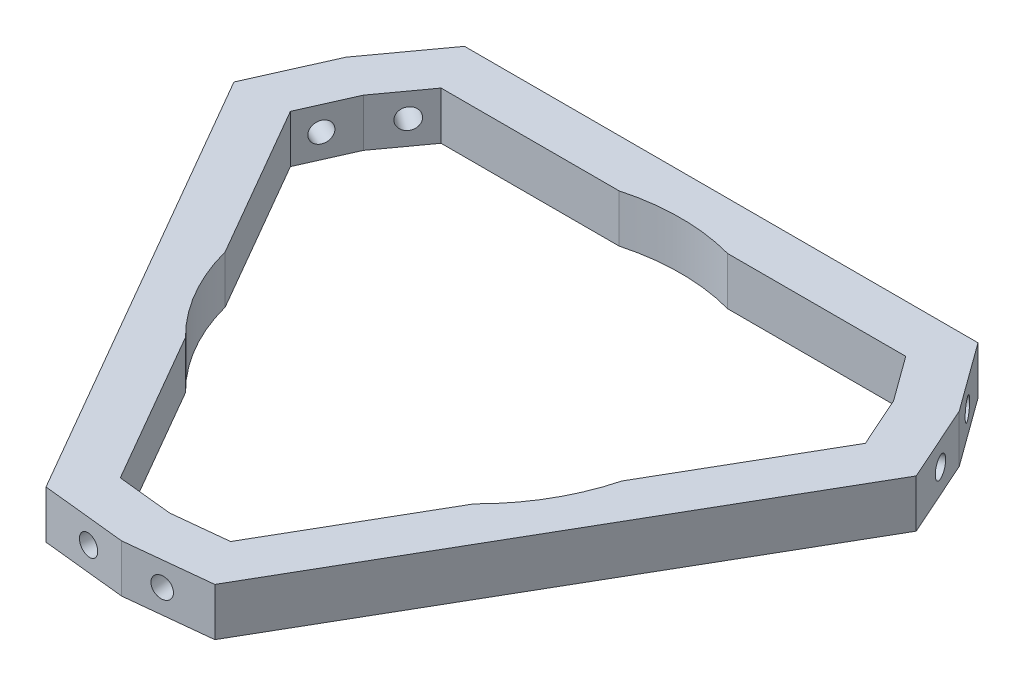
SolidWorks part; units mm, degrees
material "PET"
ref_plane "Front" through (0, 0, 0) normal (0, 0, 1) x (1, 0, 0)
ref_plane "Top" through (0, 0, 0) normal (0, 1, 0) x (1, 0, 0)
ref_plane "Right" through (0, 0, 0) normal (1, 0, 0) x (0, 0, -1)
sketch "Эскиз1" plane through (0, 0, 0) normal (0, 1, 0) x (1, 0, 0)
  line L0 (-8.6603, 5) -> (-51.9615, 30) construction
  line L4 (0, -60) -> (51.9615, 30) construction
  line L5 (51.9615, 30) -> (-51.9615, 30) construction
  line L6 (-51.9615, 30) -> (0, -60) construction
  line L7 (8.6603, 5) -> (51.9615, 30) construction
  line L8 (0, 0) -> (0, -50) construction
  line L9 (0, 0) -> (-41.6644, 30.2709)
  line L10 (0, 0) -> (-47.0476, 20.9469)
  line L11 (0, 0) -> (48.541, 35.2671)
  line L13 (54.8127, 24.4042) -> (0, 0)
  line L14 (0, 0) -> (-6.2717, -59.6713)
  line L16 (6.2717, -59.6713) -> (0, 0)
  line L17 (-49.8947, 14.5521) -> (-44.846, 25.8918)
  line L18 (-44.846, 25.8918) -> (-37.5499, 35.9341)
  line L27 (-47.6577, 19.5766) -> (-29.7377, 11.5981)
  line L28 (-40.7827, 31.4845) -> (-29.024, 22.9413)
  line L45 (0, 0) -> (-60.0777, 0) construction
  line L91 (37.5499, 35.9341) -> (44.846, 25.8918)
  line L98 (44.846, 25.8918) -> (49.8947, 14.5521)
  line L101 (40.7827, 31.4845) -> (24.9131, 19.9545)
  line L107 (47.6577, 19.5766) -> (34.3797, 13.6649)
  line L121 (12.3449, -50.4862) -> (0, -51.7837)
  line L122 (0, -51.7837) -> (-12.3449, -50.4862)
  line L123 (6.875, -51.0611) -> (4.8246, -31.5526)
  line L124 (-6.875, -51.0611) -> (-5.3557, -36.6062)
  line L125 (37.5499, 35.9341) -> (-37.5499, 35.9341)
  line L126 (-49.8947, 14.5521) -> (-12.3449, -50.4862)
  line L127 (12.3449, -50.4862) -> (49.8947, 14.5521)
  line L131 (8.066, -43.8973) -> (42.0492, 14.9633)
  line L132 (38.7504, 22.3726) -> (42.0492, 14.9633)
  line L133 (33.9832, 28.9341) -> (38.7504, 22.3726)
  line L134 (33.9832, 28.9341) -> (-33.9832, 28.9341)
  line L135 (-38.7504, 22.3726) -> (-33.9832, 28.9341)
  line L136 (-42.0492, 14.9633) -> (-38.7504, 22.3726)
  line L137 (-42.0492, 14.9633) -> (-8.066, -43.8973)
  line L138 (0, -44.7451) -> (-8.066, -43.8973)
  line L139 (8.066, -43.8973) -> (0, -44.7451)
  circle A1 centre (0, 0) radius 60 construction
  circle A2 centre (0, 0) radius 51.5 construction
  circle A3 centre (0, 0) radius 30
  point P21 (0, 0)
  point P44 (-0.2291, 0.1323)
  point P47 (-4.0451, 2.3354)
  point P49 (0, 0)
  point P69 (-0.0303, 0.0175)
  point P90 (2.4271, -1.4013)
  dimension "D1" = 120
  dimension "D9" = 8.5
  dimension "D10" = 103
  dimension "D11" = 7
  dimension "D14" = 1.5
  dimension "D17" = 108
  dimension "D16" = 60
  dimension "D2" = 6
  dimension "D3" = 6
  dimension "D4" = 10.7664
  dimension "D5" = 6
  dimension "D6" = 6
  dimension "D7" = 3
  dimension "D8" = 6
  dimension "D12" = 7
  dimension "D13" = 7
extrude "Бобышка-Вытянуть1" add sketch "Эскиз1" along normal mid plane 7 contours L10 L136 L135 L9 L18 L17 | L9 L135 L28 L18 | A3 L134 L133 L101 L91 L125 L18 L28 L135 | L11 L133 L132 L13 L98 L91 | L101 L133 L11 L91 | L13 L132 L107 L98 | A3 L131 L139 L123 L121 L127 L98 L107 L132 | L123 L139 L16 L121 | L16 L139 L138 L14 L122 L121 | L14 L138 L124 L122 | A3 L137 L136 L27 L17 L126 L122 L124 L138 | L27 L136 L10 L17 region at (-41.6435, 0, -24.0429) region at (-38.392, 0, -28.8205) region at (0, 0, -32.4502) region at (-44.1552, 0, -18.8382) region at (-28.1027, 0, 16.2251) region at (38.392, 0, -28.8205) region at (41.6435, 0, -24.0429) region at (44.1552, 0, -18.8382) region at (0, 0, 48.0858) region at (-5.7633, 0, 47.6587) region at (5.7633, 0, 47.6587) region at (28.1027, 0, 16.2251)
revolve "Вырез-Повернуть1" cut sketch "Эскиз1<3>" angle 360 about L10 region at (-44.1552, 0, -18.8382)
sketch "Эскиз1<3>" plane through (0, 0, 0) normal (0, 1, 0) x (1, 0, 0) same geometry as "Эскиз1"
revolve "Вырез-Повернуть2" cut sketch "Эскиз1<4>" angle 360 about L9 region at (-38.392, 0, -28.8205)
sketch "Эскиз1<4>" plane through (0, 0, 0) normal (0, 1, 0) x (1, 0, 0) same geometry as "Эскиз1"
pattern_circular "Круговой массив1" count 3 over 360 about axis through (0, 3.5, 0) along (0, -1, 0) of "Вырез-Повернуть2", "Вырез-Повернуть1" reverse direction yes
